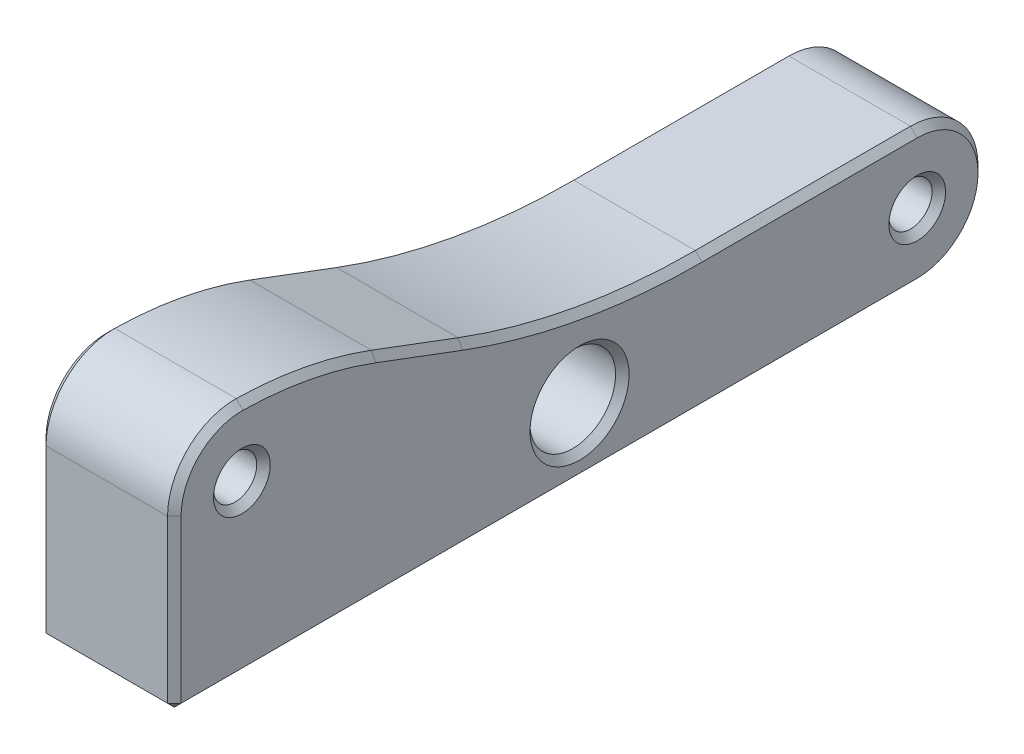
SolidWorks part; units mm, degrees
ref_plane "Front Plane" through (0, 0, 0) normal (0, 0, 1) x (1, 0, 0)
ref_plane "Top Plane" through (0, 0, 0) normal (0, 1, 0) x (1, 0, 0)
ref_plane "Right Plane" through (0, 0, 0) normal (1, 0, 0) x (0, 0, -1)
sketch "Sketch1" plane through (0, 0, 0) normal (0, 1, 0) x (1, 0, 0)
  line L1 (6.35, -38.1) -> (-6.35, -38.1)
  line L2 (6.35, -38.1) -> (6.35, 38.1)
  line L3 (6.35, 38.1) -> (-6.35, 38.1)
  line L4 (-6.35, -38.1) -> (-6.35, 38.1)
  line L5 (6.35, -38.1) -> (-6.35, 38.1) construction
  line L6 (6.35, 38.1) -> (-6.35, -38.1) construction
  point P0 (0, 0)
  point P9 (0, 0)
  dimension "D1" = 12.7
  dimension "D2" = 76.2
extrude "Boss-Extrude3" add sketch "Sketch1" along normal blind 12.7
sketch "Sketch3" plane through (0, 0, 0) normal (0, -1, 0) x (1, 0, 0)
  line L1 (6.35, 38.1) -> (6.35, -38.1) construction
  line L2 (-6.35, 38.1) -> (6.35, 38.1)
  line L3 (-6.35, 38.1) -> (-6.35, -38.1)
  line L4 (-6.35, -38.1) -> (6.35, -38.1)
  line L5 (6.35, 38.1) -> (6.35, -38.1)
  line L6 (-6.35, 38.1) -> (6.35, -38.1) construction
  line L7 (-6.35, -38.1) -> (6.35, 38.1) construction
  line L8 (6.35, -38.1) -> (-6.35, -38.1) construction
  point P3 (0, 0)
  point P4 (0, 0)
extrude "Boss-Extrude4" add sketch "Sketch3" along normal blind 9.525
sketch "Sketch9" plane through (-6.35, 0, 0) normal (-1, 0, 0) x (0, 0, 1)
  line L0 (-38.1, 12.7) -> (-38.1, -9.525)
  line L1 (38.1, -9.525) -> (-38.1, -9.525) construction
  line L2 (-38.1, -9.525) -> (38.1, -9.525)
  line L3 (38.1, 12.7) -> (38.1, -9.525) construction
  line L4 (38.1, -9.525) -> (38.1, 12.7)
  line L5 (-38.1, 3.175) -> (0, 3.175)
  line L6 (0, 3.175) -> (25.4, 12.7)
  line L9 (-38.1, 12.7) -> (38.1, 12.7)
  line L14 (0, -3.175) -> (-31.75, -3.175)
  circle A0 centre (0, -3.175) radius 4.025
  circle A1 centre (-31.75, -3.175) radius 2.032
  circle A2 centre (31.75, 6.35) radius 2.032
  line M3 (-38.1, 12.7) -> (-38.1, -9.525)
  line M6 (38.1, 12.7) -> (-38.1, 12.7)
  dimension "D1" = 8.05
  dimension "D5" = 4.064
  dimension "D6" = 4.064
  dimension "D2" = 38.1
  dimension "D3" = 6.35
  dimension "D4" = 31.75
  dimension "D7" = 6.35
  dimension "D8" = 6.35
  dimension "D9" = 38.1
  dimension "D10" = 12.7
  dimension "D11" = 12.7
extrude "Cut-Extrude2" cut sketch "Sketch9" against normal through all contours A1 L14 | A2 | A0 | A1 region at (-6.35, -3.175, -33.7245) region at (-6.35, 6.35, 31.75)
extrude "Cut-Extrude4" cut sketch "Sketch9<5>" against normal through all and the other way through all contours L5 L6 M6 M3
sketch "Sketch9<5>" plane through (-6.35, 0, 0) normal (-1, 0, 0) x (0, 0, 1) same geometry as "Sketch9"
fillet "Fillet6" radius 6.35 1 edges at (0, 3.175, -38.1)
fillet "Fillet7" radius 63.5 1 edges at (0, 3.175, 0)
fillet "Fillet8" radius 38.1 1 edges at (0, 12.7, 25.4)
fillet "Fillet9" radius 6.35 1 edges at (0, 12.7, 38.1)
chamfer "Chamfer4" distance 0.635 angle 45 6 edges at (6.35, 6.35, 33.782) (6.35, -3.175, 4.025) (6.35, -3.175, -29.718) (-6.35, 6.35, 33.782) (-6.35, -3.175, -29.718) (-6.35, -3.175, 4.025)
fillet "Fillet10" radius 6.35 1 edges at (0, -9.525, -38.1)
chamfer "Chamfer5" distance 0.635 angle 45 19 edges at (-6.35, -1.59, 38.1) (-6.35, 10.8746, 36.2004) (-6.35, 12.0273, 25.1812) (-6.35, 8.7461, 14.8563) (-6.35, 4.1939, -0.1848) (-6.35, 3.175, -21.6324) (-6.35, 1.3151, -36.2401) (6.35, 1.3151, -36.2401) (6.35, 3.175, -21.6324) (6.35, 4.1939, -0.1848) (6.35, -1.59, 38.1) (6.35, 8.7461, 14.8563) (6.35, 10.8746, 36.2004) (6.35, 12.0273, 25.1812) (0, -9.525, 38.1) (-6.35, -9.525, 3.175) (6.35, -9.525, 3.175) (-6.35, -7.6651, -36.2401) (6.35, -7.6651, -36.2401)
